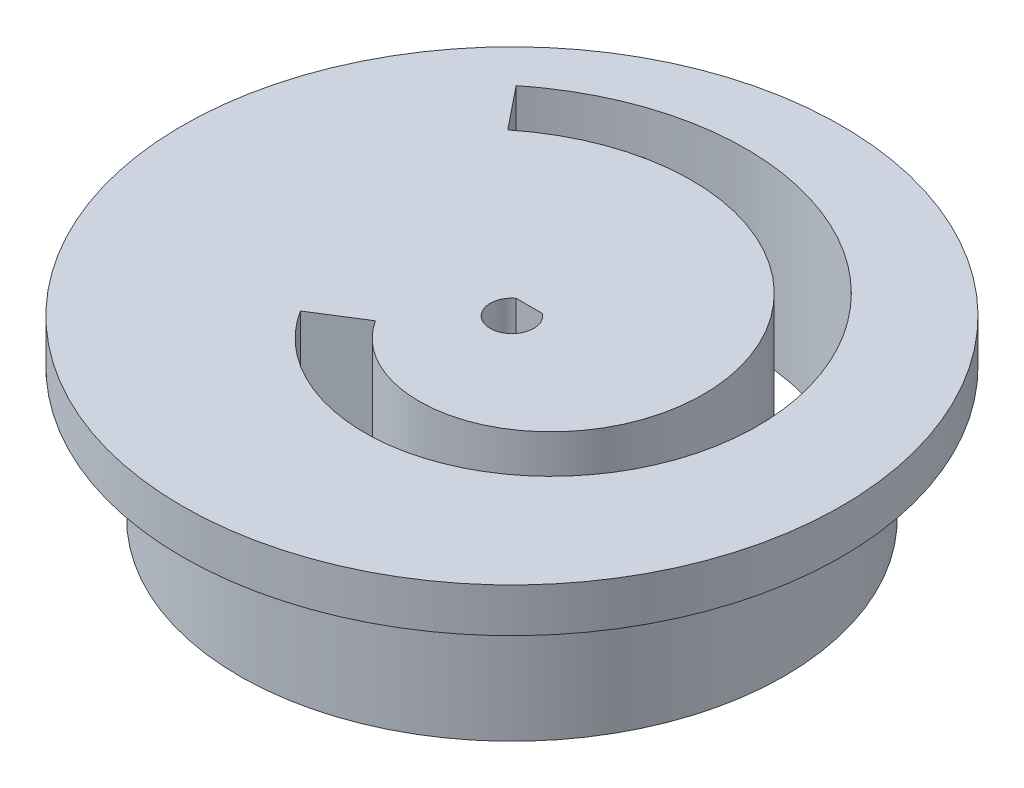
SolidWorks part; units mm, degrees
ref_plane "Front Plane" through (0, 0, 0) normal (0, 0, 1) x (1, 0, 0)
ref_plane "Top Plane" through (0, 0, 0) normal (0, 1, 0) x (1, 0, 0)
ref_plane "Right Plane" through (0, 0, 0) normal (1, 0, 0) x (0, 0, -1)
sketch "Sketch1" plane through (0, 0, 0) normal (0, 1, 0) x (1, 0, 0)
  circle A0 centre (0, 0) radius 37.5
  dimension "D1" = 75
extrude "Boss-Extrude1" add sketch "Sketch1" along normal blind 5
sketch "Sketch2" plane through (0, 5, 0) normal (0, 1, 0) x (1, 0, 0)
  circle A0 centre (0, 0) radius 29
  dimension "D1" = 58
curve "Helix/Spiral1"
ref_plane "Plane1" through (-20.5061, 5, -20.5061) normal (0.78, 0, -0.6257) x (-0.6257, 0, -0.78)
sketch "Sketch9" plane through (-20.5061, 5, -20.5061) normal (0.78, 0, -0.6257) x (-0.6257, 0, -0.78)
  line L7 (-21.0269, 1.4328) -> (-14.8269, 1.4328)
  line L8 (-21.0269, 1.4328) -> (-21.0269, -1.5672)
  line L9 (-21.0269, -1.5672) -> (-14.8269, -1.5672)
  line L10 (-14.8269, 1.4328) -> (-14.8269, -1.5672)
  dimension "D2" = 3
  dimension "D3" = 23.5
sweep "Cut-Sweep1" [suppressed] cut profiles "Sketch9" path "Helix/Spiral1"
sketch "Sketch10" plane through (0, 0, 0) normal (0, -1, 0) x (1, 0, 0)
  circle A0 centre (0, 0) radius 31
  dimension "D1" = 62
extrude "Boss-Extrude2" add sketch "Sketch10" along normal blind 15
sketch "Sketch11" plane through (0, -15, 0) normal (0, -1, 0) x (1, 0, 0)
  line L0 (1.4916, -1.975) -> (-1.4916, -1.975)
  arc A0 (1.4916, -1.975) -> (-1.4916, -1.975) centre (0, 0) ccw
  point P1 (0, 0)
  point P5 (0, 2.475)
  dimension "D1" = 4.95
  dimension "D2" = 4.45
extrude "Cut-Extrude1" cut sketch "Sketch11" against normal through all
sketch "Sketch12" plane through (0, 5, 0) normal (0, 1, 0) x (1, 0, 0)
  line L0 (-12.523, -11.551) -> (-7.276, -8.248)
  line L1 (-22.4459, 22.9242) -> (-18.5663, 18.088)
  spline S2 degree 3 poles (2960.9219, -21.7843) (-70.995, -337.6225) (-78.491, -4.4964) (-9.7961, 22.7763) (-7.4087, 23.3253) (-2.6824, 23.7019) (-0.3315, 23.5309) (4.1174, 22.5401) (6.2273, 21.718) (10.0278, 19.5516) (11.729, 18.2016) (14.5963, 15.1446) (15.7709, 13.429) (17.5276, 9.8265) (18.1153, 7.9288) (18.7004, 4.1491) (18.7001, 2.2551) (18.1668, -1.3471) (17.6323, -3.0675) (16.134, -6.1843) (15.165, -7.592) (12.933, -9.9887) (11.6617, -10.9869) (8.9762, -12.5193) (7.5513, -13.0598) (4.7097, -13.6811) (3.2807, -13.7648) (0.5659, -13.5227) (-0.7326, -13.196) (-3.08, -12.2195) (-4.1409, -11.565) (-36.9001, 16.0741) (117.1944, 186.1465) (1532.1946, -2575.8624) knots -1.751027 -1.751027 -1.751027 -1.751027 0.0625 0.0625 0.125 0.125 0.1875 0.1875 0.25 0.25 0.3125 0.3125 0.375 0.375 0.4375 0.4375 0.5 0.5 0.5625 0.5625 0.625 0.625 0.6875 0.6875 0.75 0.75 0.8125 0.8125 0.875 0.875 0.9375 0.9375 3.14597 3.14597 3.14597 3.14597 only from (-18.5663, 18.088) to (-7.276, -8.248)
  spline S3 degree 3 poles (-18.5663, 18.088) (-16.5741, 19.6861) (-14.3733, 20.9591) (-9.7961, 22.7763) (-7.4087, 23.3253) (-2.6824, 23.7019) (-0.3315, 23.5309) (4.1174, 22.5401) (6.2273, 21.718) (10.0278, 19.5516) (11.729, 18.2016) (14.5963, 15.1446) (15.7709, 13.429) (17.5276, 9.8265) (18.1153, 7.9288) (18.7004, 4.1491) (18.7001, 2.2551) (18.1668, -1.3471) (17.6323, -3.0675) (16.134, -6.1843) (15.165, -7.592) (12.933, -9.9887) (11.6617, -10.9869) (8.9762, -12.5193) (7.5513, -13.0598) (4.7097, -13.6811) (3.2807, -13.7648) (0.5659, -13.5227) (-0.7326, -13.196) (-3.08, -12.2195) (-4.1409, -11.565) (-5.944, -10.0437) (-6.6967, -9.1683) (-7.276, -8.248) knots 0 0 0 0 0.0625 0.0625 0.125 0.125 0.1875 0.1875 0.25 0.25 0.3125 0.3125 0.375 0.375 0.4375 0.4375 0.5 0.5 0.5625 0.5625 0.625 0.625 0.6875 0.6875 0.75 0.75 0.8125 0.8125 0.875 0.875 0.9375 0.9375 1 1 1 1
  spline S4 degree 3 poles (2938.0641, -218.9124) (-68.9317, -401.9287) (-96.4251, -4.9457) (-11.507, 28.7678) (-8.5206, 29.4563) (-2.5557, 29.9317) (0.4093, 29.7179) (6.0721, 28.4567) (8.7569, 27.4126) (13.639, 24.6296) (15.8247, 22.8976) (19.5448, 18.9315) (21.0701, 16.7074) (23.3738, 11.983) (24.1466, 9.495) (24.9231, 4.4801) (24.9249, 1.9664) (24.2082, -2.8744) (23.492, -5.1883) (21.4501, -9.4358) (20.1306, -11.3574) (17.0417, -14.6742) (15.2817, -16.0597) (11.5014, -18.2167) (9.4931, -18.9817) (5.4165, -19.873) (3.3616, -19.9967) (-0.6165, -19.6419) (-2.5262, -19.165) (-6.0493, -17.6993) (-7.6501, -16.7162) (-58.6755, 26.3342) (173.2187, 298.1342) (1874.8542, -2321.6431) knots -1.727175 -1.727175 -1.727175 -1.727175 0.0625 0.0625 0.125 0.125 0.1875 0.1875 0.25 0.25 0.3125 0.3125 0.375 0.375 0.4375 0.4375 0.5 0.5 0.5625 0.5625 0.625 0.625 0.6875 0.6875 0.75 0.75 0.8125 0.8125 0.875 0.875 0.9375 0.9375 3.168566 3.168566 3.168566 3.168566 only from (-22.4459, 22.9242) to (-12.523, -11.551)
  spline S5 degree 3 poles (-22.4459, 22.9242) (-19.9698, 24.9105) (-17.2379, 26.4925) (-11.507, 28.7678) (-8.5206, 29.4563) (-2.5557, 29.9317) (0.4093, 29.7179) (6.0721, 28.4567) (8.7569, 27.4126) (13.639, 24.6296) (15.8247, 22.8976) (19.5448, 18.9315) (21.0701, 16.7074) (23.3738, 11.983) (24.1466, 9.495) (24.9231, 4.4801) (24.9249, 1.9664) (24.2082, -2.8744) (23.492, -5.1883) (21.4501, -9.4358) (20.1306, -11.3574) (17.0417, -14.6742) (15.2817, -16.0597) (11.5014, -18.2167) (9.4931, -18.9817) (5.4165, -19.873) (3.3616, -19.9967) (-0.6165, -19.6419) (-2.5262, -19.165) (-6.0493, -17.6993) (-7.6501, -16.7162) (-10.431, -14.3699) (-11.6005, -13.0164) (-12.523, -11.551) knots 0 0 0 0 0.0625 0.0625 0.125 0.125 0.1875 0.1875 0.25 0.25 0.3125 0.3125 0.375 0.375 0.4375 0.4375 0.5 0.5 0.5625 0.5625 0.625 0.625 0.6875 0.6875 0.75 0.75 0.8125 0.8125 0.875 0.875 0.9375 0.9375 1 1 1 1
  dimension "D1" = 3.1
  dimension "D2" = 3.1
sketch "Sketch13" plane through (0, 5, 0) normal (0, 1, 0) x (1, 0, 0)
  circle A0 centre (0, 0) radius 34.4168
extrude "Cut-Extrude2" cut sketch "Sketch12" against normal through all
equation "\"spiralD\"= 75"
equation "\"D1@Sketch1\"=\"spiralD\""
equation "\"spiralHeight\"= 5"
equation "\"D1@Boss-Extrude1\"=\"spiralHeight\""
equation "\"spiralHoleWidth\"=6.2"
equation "\"spiralED\"= 58"
equation "\"D1@Sketch2\"=\"spiralED\""
equation "\"D1@Sketch9\"=\"spiralHoleWidth\""
equation "\"spiralHoleHeight\"=3"
equation "\"D2@Sketch9\"=\"spiralHoleHeight\""
equation "\"axisLength\"=10"
equation "\"axisHeight\"=2"
equation "\"bitDepth\"=1"
equation "\"bitD\"=1"
equation "\"colletDepth\"=15"
equation "\"D1@Boss-Extrude2\"=\"colletDepth\""
equation "\"colletDiam\"=62"
equation "\"D1@Sketch10\"=\"colletDiam\""
equation "\"colletInnerDiam\" =4.95"
equation "\"D1@Sketch11\"=\"colletInnerDiam\""
